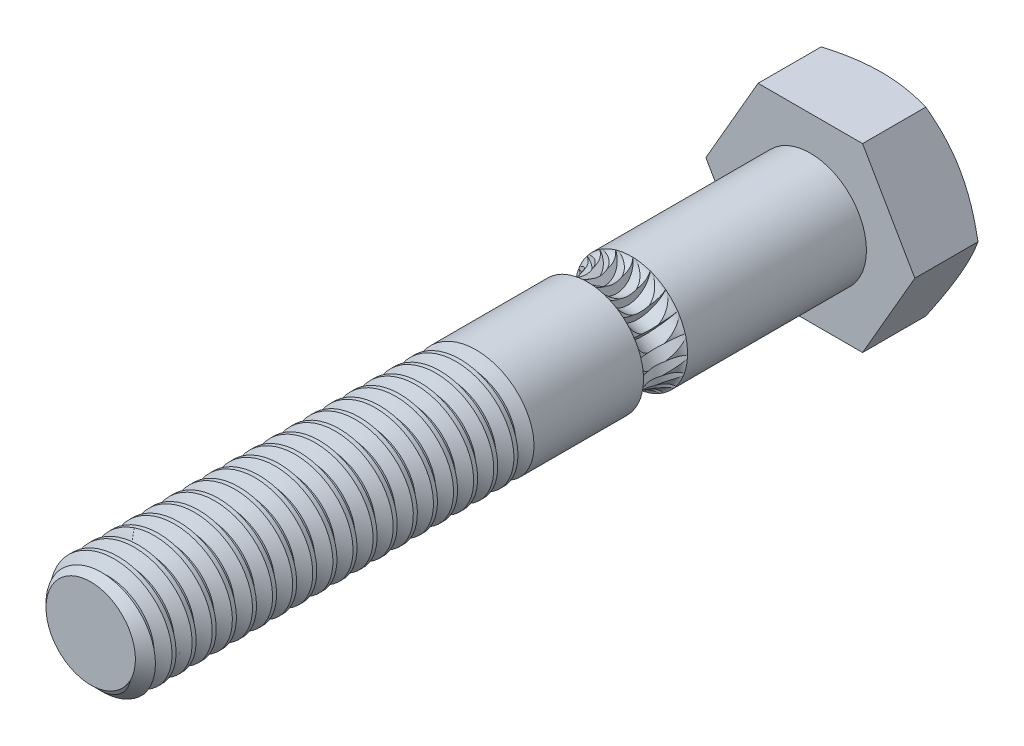
SolidWorks part; units mm, degrees
note: '?' marks a value the reader was unsure of.
ref_plane "Front Plane" through (0, 0, 0) normal (0, 0, 1) x (1, 0, 0)
ref_plane "Top Plane" through (0, 0, 0) normal (0, 1, 0) x (1, 0, 0)
ref_plane "Right Plane" through (0, 0, 0) normal (1, 0, 0) x (0, 0, -1)
sketch "Sketch1" plane through (0, 0, 0) normal (0, 0, 1) x (1, 0, 0)
  circle A0 centre (0, 0) radius 3.937
  dimension "D1" = 7.874
extrude "Bolt Body" add sketch "Sketch1" along normal blind 50.5
chamfer "Bolt Tip Chamfer" distance 0.8 angle 45 1 edges at (3.937, 0, 50.5)
sketch "Sketch7" plane through (0, 0, 0) normal (1, 0, 0) x (0, 0, -1)
  line L0 (-50.5, 3.937) -> (-50.9619, 3.137)
  line L1 (-50.9619, 3.137) -> (-51.167, 3.137)
  line L2 (-51.167, 3.137) -> (-51.6289, 3.937)
  line L3 (-51.6289, 3.937) -> (-50.5, 3.937)
  line L4 (-50.5, 3.137) -> (-50.5, -3.137) construction
  line L5 (0, 3.937) -> (-49.7, 3.937) construction
  dimension "D1" = 60
  dimension "D2" = 60
  dimension "D3" = 0.8
  dimension "D4" = 1.1289
sketch "Sketch8" plane through (0, 0, 50.5) normal (0, 0, 1) x (1, 0, 0)
  circle A0 centre (0, 0) radius 4
curve "Helix/Spiral1" pitch 1.4111 height 28.2222 turns 20
sweep "Cut-Sweep1" cut profiles "Sketch7" path "Helix/Spiral1"
ref_axis "Bolt Axis" through (0, 0, -10.3812) along (0, 0, 1)?
sketch "Sketch3" plane through (0, 0, 0) normal (0, 0, 1) x (1, 0, 0)
  line L1 (7.3323, 0) -> (3.6662, 6.35)
  line L2 (3.6662, 6.35) -> (-3.6662, 6.35)
  line L3 (-3.6662, 6.35) -> (-7.3323, 0)
  line L4 (-7.3323, 0) -> (-3.6662, -6.35)
  line L5 (-3.6662, -6.35) -> (3.6662, -6.35)
  line L6 (3.6662, -6.35) -> (7.3323, 0)
  circle A1 centre (0, 0) radius 6.35 construction
  dimension "D2" = 12.7
extrude "Bolt Head" add sketch "Sketch3" against normal blind 5
sketch "Sketch6" plane through (0, 0, -5) normal (0, 0, -1) x (-1, 0, 0)
  circle A0 centre (0, 0) radius 6.35
extrude "Head Circle" cut sketch "Sketch6" against normal blind 10 draft 60 flip side to cut
ref_plane "Waist Cut Plane" through (0, 3.05, 0) normal (0, 1, 0) x (1, 0, 0)
sketch "Waist Cut Contour" plane through (0, 3.05, 0) normal (0, 1, 0) x (1, 0, 0)
  line L0 (0, 10.3812) -> (0, -69.3803) construction
  circle A0 centre (-2.85, -14.1) radius 1.5875
  dimension "D2" = 3.175
  dimension "D1" = 14.1
  dimension "D3" = 2.85
ref_plane "Waist Revolve Plane" through (0, 0, 14.1) normal (0, 0, 1) x (1, 0, 0)
sketch "Waist Cut Path" plane through (0, 0, 14.1) normal (0, 0, 1) x (1, 0, 0)
  circle A0 centre (0, 0) radius 4.1743
sweep "Waist Cut" cut profiles "Waist Cut Contour" path "Waist Cut Path"
ref_plane "Tooth Plane" through (0, 1.31, 0) normal (0, 1, 0) x (1, 0, 0)
sketch "Tooth Cut Contour" plane through (0, 1.31, 0) normal (0, 1, 0) x (1, 0, 0)
  line L1 (0, 10.3812) -> (0, -69.3803) construction
  line L2 (-3.6662, 0) -> (-7.3323, 0) construction
  circle A0 centre (-4, -14.1) radius 1.5875
  dimension "D1" = 14.1
  dimension "D3" = 3.175
  dimension "D2" = 4
extrude "Tooth Cut" cut sketch "Tooth Cut Contour" along normal through all
pattern_circular "Tooth X20" count 20 over 360 about axis through (0, 0, 0) along (0, 0, 1) of "Tooth Cut"
sketch "Drive Diameter Metric" plane through (0, 0, 14.1) normal (0, 0, 1) x (1, 0, 0)
  line L0 (-3.2221, 0.3305) -> (3.2221, -0.3305)
  dimension "D1" = 6.4781
ref_plane "Top Zero Plane" through (0, 3.937, 0) normal (0, 1, 0) x (1, 0, 0)
